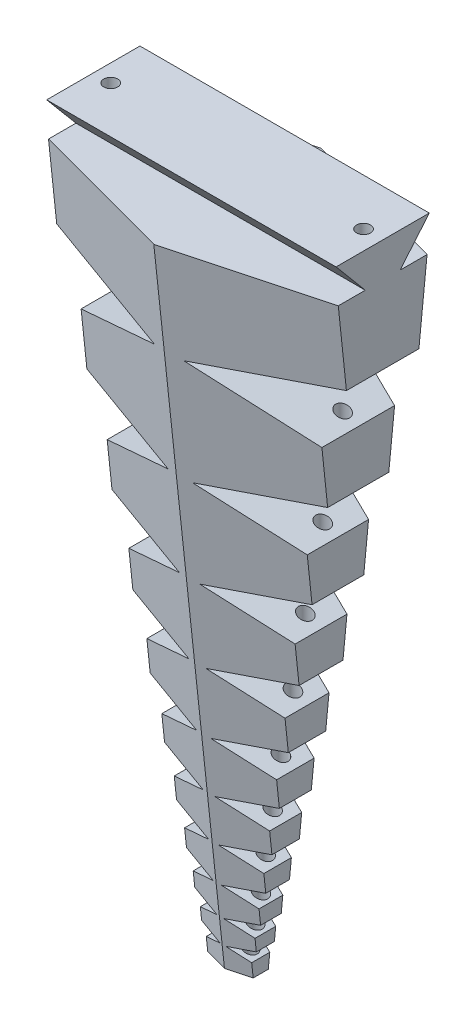
SolidWorks part; units mm, degrees
ref_plane "Front Plane" through (0, 0, 0) normal (0, 0, 1) x (1, 0, 0)
ref_plane "Top Plane" through (0, 0, 0) normal (0, 1, 0) x (1, 0, 0)
ref_plane "Right Plane" through (0, 0, 0) normal (1, 0, 0) x (0, 0, -1)
sketch "spiral_flat" plane through (0, 0, 0) normal (0, 0, 1) x (1, 0, 0)
  line L0 (3.2655, 0) -> (-3.2655, 0) construction
  line L1 (3.9293, 3.054) -> (-3.9293, 3.054) construction
  line L2 (4.728, 6.7288) -> (-4.728, 6.7288) construction
  line L3 (5.689, 11.1506) -> (-5.689, 11.1506) construction
  line L4 (6.8455, 16.4712) -> (-6.8455, 16.4712) construction
  line L5 (8.2369, 22.8733) -> (-8.2369, 22.8733) construction
  line L6 (9.9112, 30.5768) -> (-9.9112, 30.5768) construction
  line L7 (11.9259, 39.8461) -> (-11.9259, 39.8461) construction
  line L8 (14.35, 50.9996) -> (-14.35, 50.9996) construction
  line L9 (17.2669, 64.4202) -> (-17.2669, 64.4202) construction
  line L10 (20.7767, 80.5689) -> (-20.7767, 80.5689) construction
  line L11 (25, 100) -> (-25, 100) construction
  line L12 (0, -2.9617) -> (0, 103.8438) construction
  line L13 (3.2655, 0) -> (25, 100) construction
  line L14 (-3.2655, 0) -> (-25, 100) construction
  line L15 (0.3266, 0) -> (2.5, 100) construction
  line L16 (-0.3266, 0) -> (-2.5, 100) construction
  line L17 (-20.7767, 80.5689) -> (-20.7767, 100) construction
  line L18 (-17.2669, 64.4202) -> (-17.2669, 80.5689) construction
  line L19 (-14.35, 50.9996) -> (-14.35, 64.4202) construction
  line L20 (-11.9259, 39.8461) -> (-11.9259, 50.9996) construction
  line L21 (-9.9112, 30.5768) -> (-9.9112, 39.8461) construction
  line L22 (-8.2369, 22.8733) -> (-8.2369, 30.5768) construction
  line L23 (-6.8455, 16.4712) -> (-6.8455, 22.8733) construction
  line L24 (-5.689, 11.1506) -> (-5.689, 16.4712) construction
  line L25 (-4.728, 6.7288) -> (-4.728, 11.1506) construction
  line L26 (-3.9293, 3.054) -> (-3.9293, 6.7288) construction
  line L27 (-3.2655, 0) -> (-3.2655, 3.054) construction
  line L28 (20.7767, 80.5689) -> (20.7767, 100) construction
  line L29 (14.35, 50.9996) -> (14.35, 64.4202) construction
  line L30 (17.2669, 64.4202) -> (17.2669, 80.5689) construction
  line L31 (11.9259, 39.8461) -> (11.9259, 50.9996) construction
  line L32 (9.9112, 30.5768) -> (9.9112, 39.8461) construction
  line L33 (8.2369, 22.8733) -> (8.2369, 30.5768) construction
  line L34 (6.8455, 16.4712) -> (6.8455, 22.8733) construction
  line L35 (5.689, 11.1506) -> (5.689, 16.4712) construction
  line L36 (4.728, 6.7288) -> (4.728, 11.1506) construction
  line L37 (3.9293, 3.054) -> (3.9293, 6.7288) construction
  line L38 (3.2655, 0) -> (3.2655, 3.054) construction
  line L39 (-2.0777, 80.5689) -> (-17.2669, 75.0404) construction
  line L40 (-1.7267, 64.4202) -> (-17.2669, 67.1604) construction
  line L41 (-2.0777, 80.5689) -> (-20.7767, 83.866) construction
  line L42 (-1.7267, 64.4202) -> (-14.35, 59.8257) construction
  line L43 (-1.435, 50.9996) -> (-14.35, 53.2769) construction
  line L44 (-1.435, 50.9996) -> (-11.9259, 47.1812) construction
  line L45 (-1.1926, 39.8461) -> (-11.9259, 41.7387) construction
  line L46 (-1.1926, 39.8461) -> (-9.9112, 36.6728) construction
  line L47 (-0.9911, 30.5768) -> (-9.9112, 32.1496) construction
  line L48 (-0.9911, 30.5768) -> (-8.2369, 27.9395) construction
  line L49 (-0.8237, 22.8733) -> (-8.2369, 24.1805) construction
  line L50 (-0.8237, 22.8733) -> (-6.8455, 20.6816) construction
  line L51 (-0.6845, 16.4712) -> (-6.8455, 17.5576) construction
  line L52 (-0.6845, 16.4712) -> (-5.689, 14.6497) construction
  line L53 (-0.5689, 11.1506) -> (-5.689, 12.0534) construction
  line L54 (-0.5689, 11.1506) -> (-4.728, 9.6368) construction
  line L55 (-0.4728, 6.7288) -> (-4.728, 7.4791) construction
  line L56 (-0.4728, 6.7288) -> (-3.9293, 5.4708) construction
  line L57 (-0.3929, 3.054) -> (-3.9293, 3.6776) construction
  line L58 (-0.3929, 3.054) -> (-3.2655, 2.0085) construction
  line L59 (0.3929, 3.054) -> (3.2655, 2.0085) construction
  line L60 (0.3929, 3.054) -> (3.9293, 3.6776) construction
  line L61 (0.4728, 6.7288) -> (3.9293, 5.4708) construction
  line L62 (0.4728, 6.7288) -> (4.728, 7.4791) construction
  line L63 (0.5689, 11.1506) -> (4.728, 9.6368) construction
  line L64 (0.5689, 11.1506) -> (5.689, 12.0534) construction
  line L65 (0.6845, 16.4712) -> (5.689, 14.6497) construction
  line L66 (0.6845, 16.4712) -> (6.8455, 17.5576) construction
  line L67 (0.8237, 22.8733) -> (6.8455, 20.6816) construction
  line L68 (0.8237, 22.8733) -> (8.2369, 24.1805) construction
  line L69 (0.9911, 30.5768) -> (8.2369, 27.9395) construction
  line L70 (0.9911, 30.5768) -> (9.9112, 32.1496) construction
  line L71 (1.1926, 39.8461) -> (9.9112, 36.6728) construction
  line L72 (1.1926, 39.8461) -> (11.9259, 41.7387) construction
  line L73 (1.435, 50.9996) -> (11.9259, 47.1812) construction
  line L74 (1.435, 50.9996) -> (14.35, 53.2769) construction
  line L75 (1.7267, 64.4202) -> (14.35, 59.8257) construction
  line L76 (1.7267, 64.4202) -> (17.2669, 67.1604) construction
  line L77 (2.0777, 80.5689) -> (17.2669, 75.0404) construction
  line L78 (2.0777, 80.5689) -> (20.7767, 83.866) construction
  line L143 (-20.7767, 100) -> (-25, 100)
  line L144 (-25, 100) -> (-3.2655, 0)
  line L145 (-3.2655, 0) -> (-3.2655, 2.0085)
  line L146 (-0.3929, 3.054) -> (-3.9293, 3.6776)
  line L147 (-3.9293, 5.4708) -> (-0.4728, 6.7288)
  line L148 (-4.728, 7.4791) -> (-4.728, 9.6368)
  line L149 (-0.5689, 11.1506) -> (-5.689, 12.0534)
  line L150 (-5.689, 14.6497) -> (-0.6845, 16.4712)
  line L151 (-6.8455, 17.5576) -> (-6.8455, 20.6816)
  line L152 (-0.8237, 22.8733) -> (-8.2369, 24.1805)
  line L153 (-9.9112, 36.6728) -> (-1.1926, 39.8461)
  line L154 (-1.1926, 39.8461) -> (-11.9259, 41.7387)
  line L155 (-14.35, 59.8257) -> (-1.7267, 64.4202)
  line L156 (-1.7267, 64.4202) -> (-17.2669, 67.1604)
  line L157 (-17.2669, 75.0404) -> (-2.0777, 80.5689)
  line L158 (-20.7767, 83.866) -> (-20.7767, 100)
  line L159 (3.2655, 2.0085) -> (3.2655, 0)
  line L160 (0.3929, 3.054) -> (3.2655, 2.0085)
  line L161 (3.9293, 3.6776) -> (0.3929, 3.054)
  line L162 (3.9293, 5.4708) -> (3.9293, 3.6776)
  line L163 (0.4728, 6.7288) -> (3.9293, 5.4708)
  line L164 (4.728, 7.4791) -> (0.4728, 6.7288)
  line L165 (4.728, 9.6368) -> (4.728, 7.4791)
  line L166 (0.5689, 11.1506) -> (4.728, 9.6368)
  line L167 (5.689, 12.0534) -> (0.5689, 11.1506)
  line L168 (5.689, 14.6497) -> (5.689, 12.0534)
  line L169 (0.6845, 16.4712) -> (5.689, 14.6497)
  line L170 (6.8455, 17.5576) -> (0.6845, 16.4712)
  line L171 (6.8455, 20.6816) -> (6.8455, 17.5576)
  line L172 (0.8237, 22.8733) -> (6.8455, 20.6816)
  line L173 (8.2369, 24.1805) -> (0.8237, 22.8733)
  line L174 (8.2369, 27.9395) -> (8.2369, 24.1805)
  line L175 (0.9911, 30.5768) -> (8.2369, 27.9395)
  line L176 (9.9112, 32.1496) -> (0.9911, 30.5768)
  line L177 (9.9112, 36.6728) -> (9.9112, 32.1496)
  line L178 (1.1926, 39.8461) -> (9.9112, 36.6728)
  line L179 (11.9259, 41.7387) -> (1.1926, 39.8461)
  line L180 (11.9259, 47.1812) -> (11.9259, 41.7387)
  line L181 (1.435, 50.9996) -> (11.9259, 47.1812)
  line L182 (14.35, 53.2769) -> (1.435, 50.9996)
  line L183 (14.35, 59.8257) -> (14.35, 53.2769)
  line L184 (1.7267, 64.4202) -> (14.35, 59.8257)
  line L185 (17.2669, 67.1604) -> (1.7267, 64.4202)
  line L186 (17.2669, 75.0404) -> (17.2669, 67.1604)
  line L187 (2.0777, 80.5689) -> (17.2669, 75.0404)
  line L188 (20.7767, 83.866) -> (2.0777, 80.5689)
  line L189 (20.7767, 100) -> (20.7767, 83.866)
  line L190 (25, 100) -> (3.2655, 0)
  line L191 (20.7767, 100) -> (25, 100)
  line L192 (-20.7767, 83.866) -> (-2.0777, 80.5689)
  line L193 (-17.2669, 75.0404) -> (-17.2669, 67.1604)
  line L194 (-14.35, 59.8257) -> (-14.35, 53.2769)
  line L195 (-14.35, 53.2769) -> (-1.435, 50.9996)
  line L196 (-1.435, 50.9996) -> (-11.9259, 47.1812)
  line L197 (-11.9259, 47.1812) -> (-11.9259, 41.7387)
  line L198 (-9.9112, 36.6728) -> (-9.9112, 32.1496)
  line L199 (-9.9112, 32.1496) -> (-0.9911, 30.5768)
  line L200 (-0.9911, 30.5768) -> (-8.2369, 27.9395)
  line L201 (-8.2369, 27.9395) -> (-8.2369, 24.1805)
  line L202 (-6.8455, 20.6816) -> (-0.8237, 22.8733)
  line L203 (-6.8455, 17.5576) -> (-0.6845, 16.4712)
  line L204 (-5.689, 14.6497) -> (-5.689, 12.0534)
  line L205 (-0.5689, 11.1506) -> (-4.728, 9.6368)
  line L206 (-4.728, 7.4791) -> (-0.4728, 6.7288)
  line L207 (-3.9293, 5.4708) -> (-3.9293, 3.6776)
  line L208 (-0.3929, 3.054) -> (-3.2655, 2.0085)
  spline S0 degree 3 poles (0, 0) (0, 1.018) (0, 3.261) (0, 6.9778) (0, 11.4502) (0, 16.8317) (0, 23.3071) (0, 31.0987) (0, 40.4742) (0, 51.7553) (0, 65.3296) (0, 81.663) (0, 93.523) (0, 100) knots 0 0 0 0 0.03054 0.067288 0.111506 0.164712 0.228733 0.305768 0.398461 0.509996 0.644202 0.805689 1 1 1 1
  point P39 (0, 3.054)
  point P40 (0, 6.7288)
  point P41 (0, 11.1506)
  point P42 (0, 16.4712)
  point P43 (0, 22.8733)
  point P44 (0, 30.5768)
  point P45 (0, 39.8461)
  point P46 (0, 50.9996)
  point P47 (0, 64.4202)
  point P48 (0, 80.5689)
  point P49 (-0.3266, 0)
  point P50 (-0.3929, 3.054)
  point P51 (-0.4728, 6.7288)
  point P52 (-0.5689, 11.1506)
  point P53 (-0.6845, 16.4712)
  point P54 (-0.8237, 22.8733)
  point P55 (-0.9911, 30.5768)
  point P56 (-1.1926, 39.8461)
  point P57 (-1.435, 50.9996)
  point P58 (-1.7267, 64.4202)
  point P59 (-2.0777, 80.5689)
  point P60 (-2.5, 100)
  point P61 (0.3266, 0)
  point P62 (0.3929, 3.054)
  point P63 (0.4728, 6.7288)
  point P64 (0.5689, 11.1506)
  point P65 (0.6845, 16.4712)
  point P66 (0.8237, 22.8733)
  point P67 (0.9911, 30.5768)
  point P68 (1.1926, 39.8461)
  point P69 (1.435, 50.9996)
  point P70 (1.7267, 64.4202)
  point P71 (2.0777, 80.5689)
  point P72 (2.5, 100)
  dimension "D1" = 100
  dimension "D3" = 7.8586
  dimension "D2" = 6.531
  dimension "D4" = 9.456
  dimension "D5" = 11.3781
  dimension "D6" = 13.6909
  dimension "D7" = 16.4738
  dimension "D8" = 19.8224
  dimension "D9" = 23.8517
  dimension "D10" = 28.7
  dimension "D11" = 34.5338
  dimension "D12" = 41.5535
  dimension "D13" = 50
  dimension "D14" = 0.6531
  dimension "D15" = 0.7859
  dimension "D16" = 0.9456
  dimension "D17" = 1.1378
  dimension "D18" = 1.3691
  dimension "D19" = 1.6474
  dimension "D20" = 1.9822
  dimension "D21" = 2.3852
  dimension "D22" = 2.87
  dimension "D23" = 3.4534
  dimension "D24" = 4.1553
  dimension "D25" = 5
  dimension "D26" = 20
  dimension "D27" = 10
  dimension "D28" = 10
  dimension "D29" = 20
  dimension "D30" = 10
  dimension "D31" = 20
  dimension "D32" = 10
  dimension "D33" = 20
  dimension "D34" = 10
  dimension "D35" = 20
  dimension "D36" = 10
  dimension "D37" = 20
  dimension "D38" = 10
  dimension "D39" = 20
  dimension "D40" = 10
  dimension "D41" = 20
  dimension "D42" = 10
  dimension "D43" = 20
  dimension "D44" = 10
  dimension "D45" = 20
sketch "Sketch2" plane through (0, 0, 0) normal (0, 1, 0) x (1, 0, 0)
  line L0 (3.2655, 0) -> (-3.2384, 0) construction
  line L1 (0.0136, -1.9593) -> (0.0136, 1.9593) construction
  line L2 (3.2655, -1.9593) -> (3.2655, 1.9593) construction
  line L3 (-3.2384, -1.9593) -> (-3.2384, 1.9593) construction
  line L4 (3.2655, 1.9593) -> (-3.2384, 1.9593) construction
  line L5 (0.0136, 1.9593) -> (3.2655, 1.088) construction
  line L6 (3.2655, -1.9593) -> (-3.2384, -1.9593) construction
  line L7 (0.0136, -1.9593) -> (3.2655, -1.088) construction
  line L8 (0.0136, -1.9593) -> (-3.2384, -1.088) construction
  line L9 (0.0136, 1.9593) -> (-3.2384, 1.088) construction
  line L10 (0.0136, 1.9593) -> (-3.2384, 1.088)
  line L11 (-3.2384, 1.088) -> (-3.2384, -1.088)
  line L12 (-3.2384, -1.088) -> (0.0136, -1.9593)
  line L13 (0.0136, -1.9593) -> (3.2655, -1.088)
  line L14 (3.2655, -1.088) -> (3.2655, 1.088)
  line L15 (3.2655, 1.088) -> (0.0136, 1.9593)
  point P7 (0.0136, 0)
  dimension "D1" = 3.9186
  dimension "D2" = 15
ref_plane "Plane1" through (0, 100, 0) normal (0, 1, 0) x (1, 0, 0)
sketch "Sketch3" plane through (0, 100, 0) normal (0, 1, 0) x (1, 0, 0)
  line L2 (-0.1234, -12.5) -> (-0.1234, 12.5) construction
  line L5 (24.7531, 12.5) -> (-25, 12.5) construction
  line L6 (-0.1234, 12.5) -> (-25, 5.8343) construction
  line L7 (24.7531, -12.5) -> (-25, -12.5) construction
  line L8 (-0.1234, -12.5) -> (-25, -5.8343) construction
  line L9 (-0.1234, -12.5) -> (24.7531, -5.8343) construction
  line L10 (-0.1234, 12.5) -> (24.7531, 5.8343) construction
  line L12 (-25, -12.5) -> (-25, 12.5) construction
  line L15 (24.7531, -12.5) -> (24.7531, 12.5) construction
  line L16 (-0.1234, 12.5) -> (-25, 5.8343)
  line L17 (-25, 5.8343) -> (-25, -5.8343)
  line L18 (-25, -5.8343) -> (-0.1234, -12.5)
  line L19 (-0.1234, -12.5) -> (24.7531, -5.8343)
  line L20 (24.7531, -5.8343) -> (24.7531, 5.8343)
  line L21 (24.7531, 5.8343) -> (-0.1234, 12.5)
  point P8 (-0.1234, 0)
  dimension "D1" = 25
  dimension "D2" = 15
  dimension "D3" = 0.1234
  dimension "D4" = 24.8766
loft "Loft1" add profiles "Sketch2", "Sketch3" connector at (3.2655, 0, -1.0879) connector at (24.7531, 100, -5.8343)
extrude "Cut-Extrude2" cut sketch "spiral_flat" against normal through all both and the other way through all contours L192 L157 L193 L156 L155 L194 L195 L196 L197 L154 L153 L198 L199 L200 L201 L152 L202 L151 L203 L150 L204 L149 L205 L148 L206 L147 L207 L146 L208 L145 L144 L143 L158 | L188 L187 L186 L185 L184 L183 L182 L181 L180 L179 L178 L177 L176 L175 L174 L173 L172 L171 L170 L169 L168 L167 L166 L165 L164 L163 L162 L161 L160 L159 L190 L191 L189
ref_plane "Plane3" through (-20.7767, 0, 0) normal (-1, 0, 0) x (0, 0, 1)
sketch "Sketch6" plane through (-20.7767, 0, 0) normal (-1, 0, 0) x (0, 0, 1)
  line L0 (0, 100) -> (0, 83.866) construction
  line L1 (26.7585, 100) -> (-26.7585, 100) construction
  line L2 (-5.2594, 83.866) -> (5.2594, 83.866) construction
  line L3 (24.3259, 95) -> (-24.3259, 95) construction
  line L4 (2.5, 95) -> (6.6955, 100) construction
  line L5 (-2.5, 95) -> (-6.6955, 100) construction
  line L6 (2.5, 95) -> (6.6955, 100)
  line L7 (6.6955, 100) -> (6.966, 100)
  line L8 (6.966, 100) -> (5.2594, 83.866) construction
  line L9 (6.966, 100) -> (6.4371, 95)
  line L10 (6.4371, 95) -> (2.5, 95)
  line L11 (-2.5, 95) -> (-6.6955, 100)
  line L12 (-6.6955, 100) -> (-6.966, 100)
  line L13 (-6.966, 100) -> (-6.4371, 95)
  line L14 (-5.2594, 83.866) -> (-6.966, 100) construction
  line L15 (-6.4371, 95) -> (-2.5, 95)
  point P6 (0, 95)
  point P7 (-2.5, 95)
  point P10 (0, 95)
  point P11 (2.5, 95)
  dimension "D1" = 5
  dimension "D2" = 5
  dimension "D3" = 50
sketch "Sketch16" plane through (0, 0, 0) normal (0, -1, 0) x (-1, 0, 0)
  line L0 (-0.0136, -1.9593) -> (-0.0136, 1.9593) construction
  line L1 (-3.2655, 0) -> (3.2384, 0) construction
  circle A0 centre (1.7364, 0) radius 1
  circle A1 centre (-1.7636, 0) radius 1
  point P4 (-1.7636, 0)
  point P5 (1.7364, 0)
  dimension "D2" = 2
  dimension "D1" = 3.5
sketch "Sketch17" plane through (0, 100, 0) normal (0, 1, 0) x (1, 0, 0)
  line L0 (-0.1234, 12.5) -> (-0.1234, -12.5) construction
  line L1 (-20.7767, 0) -> (20.7767, 0) construction
  line L2 (-20.7767, -24.3259) -> (-20.7767, 24.3259) construction
  line L3 (20.7767, 6.8998) -> (20.7767, -6.8998) construction
  circle A1 centre (-18.2767, 0) radius 1
  circle A2 centre (18.0299, 0) radius 1
  point P10 (-18.2767, 0)
  point P17 (18.0299, 0)
  dimension "D2" = 2
  dimension "D1" = 2.5
sketch3d "3DSketch1"
  line L0 (18.0299, 100, 0) -> (1.7636, 0, 0) construction
  line L1 (-18.2767, 100, 0) -> (-1.7364, 0, 0) construction
sketch3d "3DSketch2"
  line L0 (-18.2767, 100, 0) -> (-18.2767, 79.6825, 0) construction
  line L1 (18.0299, 100, 0) -> (18.0299, 79.6788, 0) construction
extrude "Cut-Extrude3" cut sketch "Sketch17" against normal blind 20 contours A1 | A2
ref_plane "Plane5" through (0, 80.5689, 0) normal (0, -1, 0) x (-1, 0, 0)
sketch "Sketch22" plane through (0, 80.5689, 0) normal (0, -1, 0) x (-1, 0, 0)
  line L0 (18.2767, 0) -> (-18.0299, 0) construction
  line L2 (0.1234, -12.5) -> (0.1234, 12.5) construction
  circle A0 centre (15.2767, 0) radius 1
  circle A1 centre (-15.0299, 0) radius 1
  point P4 (15.2767, 0)
  point P11 (-15.0299, 0)
  dimension "D2" = 2
  dimension "D1" = 3
extrude "Cut-Extrude4" cut sketch "Sketch22" along normal blind 20
ref_plane "Plane6" through (0, 64.4202, 0) normal (0, -1, 0) x (-1, 0, 0)
sketch "Sketch23" plane through (0, 64.4202, 0) normal (0, -1, 0) x (-1, 0, 0)
  line L0 (15.2767, 0) -> (-15.0299, 0) construction
  line L1 (0.0549, 7.2297) -> (0.0549, -7.2297) construction
  line L2 (-0.0136, 1.9593) -> (0.1234, 12.5) construction
  line L3 (-0.0136, -1.9593) -> (0.1234, -12.5) construction
  circle A0 centre (12.2767, 0) radius 1
  circle A1 centre (-12.1669, 0) radius 1
  point P10 (12.2767, 0)
  point P13 (-12.1669, 0)
  dimension "D2" = 2
  dimension "D1" = 3
extrude "Cut-Extrude5" cut sketch "Sketch23" along normal blind 15
ref_plane "Plane7" through (0, 50.9996, 0) normal (0, -1, 0) x (-1, 0, 0)
sketch "Sketch24" plane through (0, 50.9996, 0) normal (0, -1, 0) x (-1, 0, 0)
  line L0 (-12.1669, 0) -> (12.2767, 0) construction
  line L1 (0.0549, -7.7763) -> (0.0549, 7.7763) construction
  circle A0 centre (9.7767, 0) radius 1
  circle A1 centre (-9.6669, 0) radius 1
  point P4 (9.7767, 0)
  point P7 (0.0549, 0)
  point P10 (-9.6669, 0)
  dimension "D2" = 2
  dimension "D1" = 2.5
extrude "Cut-Extrude6" cut sketch "Sketch24" along normal blind 12
ref_plane "Plane8" through (0, 39.8461, 0) normal (0, -1, 0) x (-1, 0, 0)
sketch "Sketch25" plane through (0, 39.8461, 0) normal (0, -1, 0) x (-1, 0, 0)
  line L0 (9.7767, 0) -> (-9.6669, 0) construction
  line L1 (0, 0) -> (0.0549, 7.2297) construction
  line L2 (-0.0136, 1.9593) -> (0.1234, 12.5) construction
  line L3 (0, 0) -> (0.0549, -7.2297) construction
  circle A0 centre (7.7767, 0) radius 1
  circle A1 centre (-7.7758, 0.1182) radius 1
  point P10 (7.7767, 0)
  point P13 (-7.7758, 0.1182)
  dimension "D2" = 2
  dimension "D1" = 2
extrude "Cut-Extrude7" cut sketch "Sketch25" along normal blind 10
ref_plane "Plane9" through (0, 30.5768, 0) normal (0, -1, 0) x (-1, 0, 0)
sketch "Sketch26" plane through (0, 30.5768, 0) normal (0, -1, 0) x (-1, 0, 0)
  line L0 (-9.6669, 0) -> (9.7767, 0) construction
  line L1 (0.0549, 6.0441) -> (0.0549, -6.0441) construction
  circle A0 centre (-6.1669, 0) radius 1
  circle A1 centre (6.2767, 0) radius 1
  point P4 (-6.1669, 0)
  point P7 (6.2767, 0)
  point P10 (0.0549, 0)
  dimension "D2" = 2
  dimension "D1" = 3.5
extrude "Cut-Extrude8" cut sketch "Sketch26" along normal blind 8
ref_plane "Plane10" through (0, 22.8733, 0) normal (0, -1, 0) x (-1, 0, 0)
sketch "Sketch27" plane through (0, 22.8733, 0) normal (0, -1, 0) x (-1, 0, 0)
  line L0 (6.2767, 0) -> (-6.1669, 0) construction
  line L1 (0.0549, -5.3055) -> (0.0549, 5.3055) construction
  circle A0 centre (5.0767, 0) radius 1
  circle A1 centre (-4.9669, 0) radius 1
  point P4 (5.0767, 0)
  point P7 (0.0549, 0)
  point P10 (-4.9669, 0)
  dimension "D2" = 2
  dimension "D1" = 1.2
extrude "Cut-Extrude9" cut sketch "Sketch27" along normal blind 6 contours A1 | A0
ref_plane "Plane11" through (0, 16.4712, 0) normal (0, -1, 0) x (-1, 0, 0)
sketch "Sketch28" plane through (0, 16.4712, 0) normal (0, -1, 0) x (-1, 0, 0)
  line L0 (5.0767, 0) -> (-4.9669, 0) construction
  line L1 (0.0549, -4.5751) -> (0.0549, 4.5751) construction
  circle A0 centre (4.0767, 0) radius 1
  circle A1 centre (-3.9669, 0) radius 1
  point P4 (4.0767, 0)
  point P7 (0.0549, 0)
  point P10 (-3.9669, 0)
  dimension "D2" = 2
  dimension "D1" = 1
extrude "Cut-Extrude10" cut sketch "Sketch28" along normal blind 6
ref_plane "Plane12" through (0, 11.1506, 0) normal (0, -1, 0) x (-1, 0, 0)
sketch "Sketch29" plane through (0, 11.1506, 0) normal (0, -1, 0) x (-1, 0, 0)
  line L0 (4.0767, 0) -> (-3.9669, 0) construction
  line L1 (0, -3.6608) -> (0, 3.6608) construction
  circle A0 centre (3.2767, 0) radius 1
  circle A1 centre (-3.2767, 0) radius 1
  point P4 (3.2767, 0)
  point P8 (0, 0)
  point P11 (-3.2767, 0)
  dimension "D2" = 2
  dimension "D1" = 0.8
extrude "Cut-Extrude11" cut sketch "Sketch29" along normal blind 5
ref_plane "Plane13" through (0, 6.7288, 0) normal (0, -1, 0) x (-1, 0, 0)
sketch "Sketch30" plane through (0, 6.7288, 0) normal (0, -1, 0) x (-1, 0, 0)
  line L0 (3.2767, 0) -> (-3.2767, 0) construction
  line L1 (0, -4.9829) -> (0, 4.9829) construction
  circle A0 centre (2.4767, 0) radius 1
  circle A1 centre (-2.4767, 0) radius 1
  point P4 (2.4767, 0)
  point P8 (0, 0)
  point P11 (-2.4767, 0)
  dimension "D2" = 2
  dimension "D1" = 0.8
extrude "Cut-Extrude12" cut sketch "Sketch30" along normal blind 4
extrude "Cut-Extrude13" cut sketch "Sketch16" against normal blind 3 contours A0 | A1
ref_plane "Plane14" through (20.8299, 0, 0) normal (1, 0, 0) x (0, 0, -1)
sketch "Sketch31" plane through (20.8299, 0, 0) normal (1, 0, 0) x (0, 0, -1)
  line L0 (0, 100) -> (0, 83.866) construction
  line L1 (26.7527, 95) -> (2.5, 95)
  line L2 (2.5, 95) -> (6.6955, 100)
  line L3 (6.6955, 100) -> (26.7527, 100)
  line L4 (26.7585, 100) -> (-26.7585, 100) construction
  line L5 (26.7527, 100) -> (26.7527, 95)
  line L6 (-6.6955, 100) -> (-26.7527, 100)
  line L7 (-2.5, 95) -> (-6.6955, 100)
  line L8 (-26.7527, 95) -> (-2.5, 95)
  line L9 (-26.7527, 100) -> (-26.7527, 95)
  dimension "D1" = 50
extrude "Cut-Extrude14" cut sketch "Sketch31" against normal blind 50
